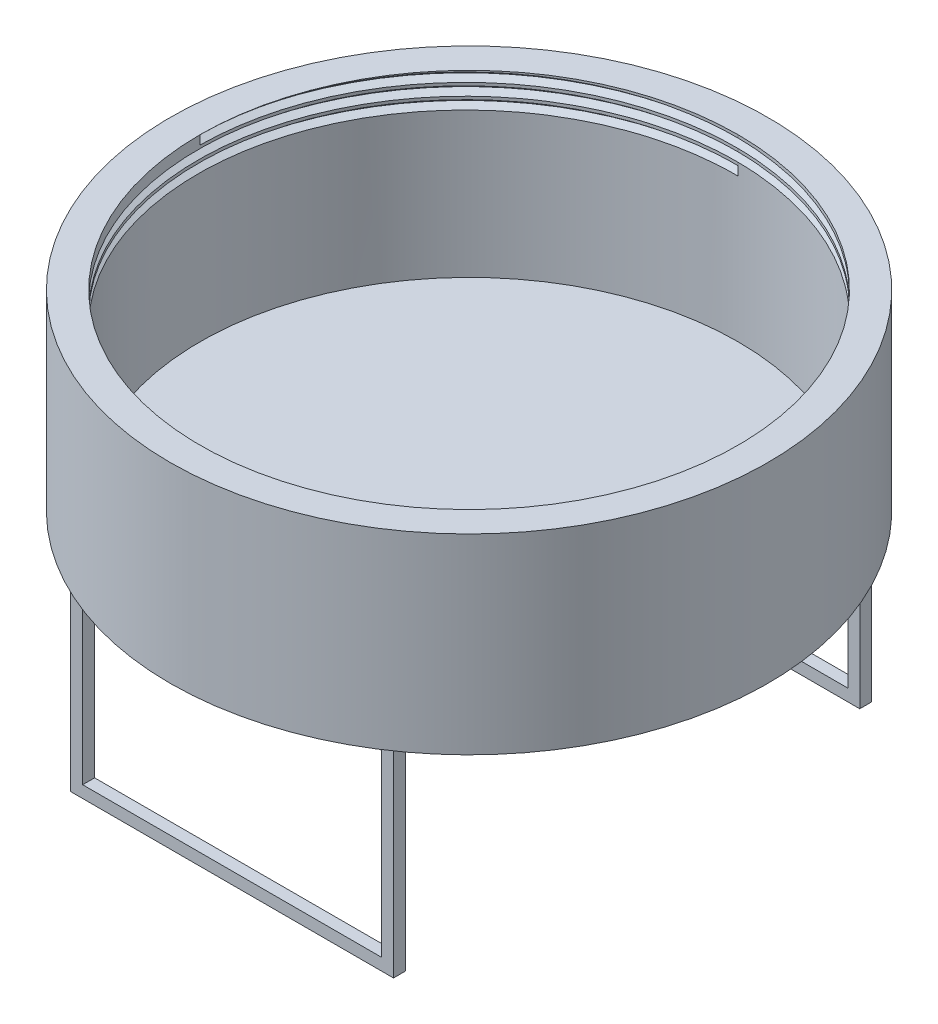
SolidWorks part; units mm, degrees
ref_plane "Front Plane" through (0, 0, 0) normal (0, 0, 1) x (1, 0, 0)
ref_plane "Top Plane" through (0, 0, 0) normal (0, 1, 0) x (1, 0, 0)
ref_plane "Right Plane" through (0, 0, 0) normal (1, 0, 0) x (0, 0, -1)
sketch "Sketch1" plane through (0, 0, 0) normal (0, 1, 0) x (1, 0, 0)
  circle A0 centre (0, 0) radius 50
  dimension "D1" = 100
extrude "Boss-Extrude1" add sketch "Sketch1" along normal blind 2 contours A0
sketch "Sketch2" plane through (0, 2, 0) normal (0, 1, 0) x (1, 0, 0)
  circle A0 centre (0, 0) radius 50
  circle A1 centre (0, 0) radius 45
  dimension "D1" = 100
  dimension "D2" = 5
extrude "Boss-Extrude2" add sketch "Sketch2" along normal blind 30
ref_plane "Plane3" through (0, 0, 40) normal (0, 0, 1) x (1, 0, 0)
sketch "Sketch5" plane through (0, 0, 40) normal (0, 0, 1) x (1, 0, 0)
  line L0 (-50, 0) -> (50, 0) construction
  line L1 (-26.6422, 0) -> (27.3578, 0)
  line L2 (-26.6422, 0) -> (-26.6422, -34)
  line L3 (-26.6422, -34) -> (27.3578, -34)
  line L4 (27.3578, 0) -> (27.3578, -34)
  line L5 (-50, 0) -> (50, 0) construction
  line L6 (-24.6422, -2) -> (25.3578, -2)
  line L7 (-24.6422, -2) -> (-24.6422, -32)
  line L8 (-24.6422, -32) -> (25.3578, -32)
  line L9 (25.3578, -2) -> (25.3578, -32)
  dimension "D1" = 2
  dimension "D2" = 2
  dimension "D3" = 2
  dimension "D4" = 2
  dimension "D5" = 50
  dimension "D6" = 2
  dimension "D7" = 30
extrude "Boss-Extrude4" add sketch "Sketch5" against normal blind 2
mirror "Mirror1" about plane through (0, 0, 0) normal (0, 0, 1) of "Boss-Extrude4"
thread "Thread1" pitch 2 method cut profile "Thread Profile1" start angle 0, offset 0, length 4.5, pitch 2, diameter 90
ref_plane "Plane4" through (-45, 32, 0) normal (0, 0, 1) x (-1, 0, 0)
sketch "Thread Profile1" plane through (-45, 32, 0) normal (0, 0, 1) x (-1, 0, 0)
  line L0 (0, 0) -> (0, 2) construction
  line L1 (0, 0) -> (1.0825, 0.625)
  line L2 (1.0825, 0.625) -> (1.0825, 0.875)
  line L3 (1.0825, 0.875) -> (0, 1.5)
  line L4 (1.0825, 0.75) -> (0, 0.75) construction
  line L11 (0, 0) -> (0, 1.5)
  point P2 (0, 0)
  dimension "Pitch" = 2
  dimension "Profile_Angle" = 60
  dimension "Profile_Land" = 0.25
  dimension "Profile_Height" = 1.0825
sketch "Sketch7" plane through (0, 0, 0) normal (0, -1, 0) x (1, 0, 0)
  line L0 (0, 0) -> (0, 50) construction
  circle A0 centre (0, 0) radius 50 construction
